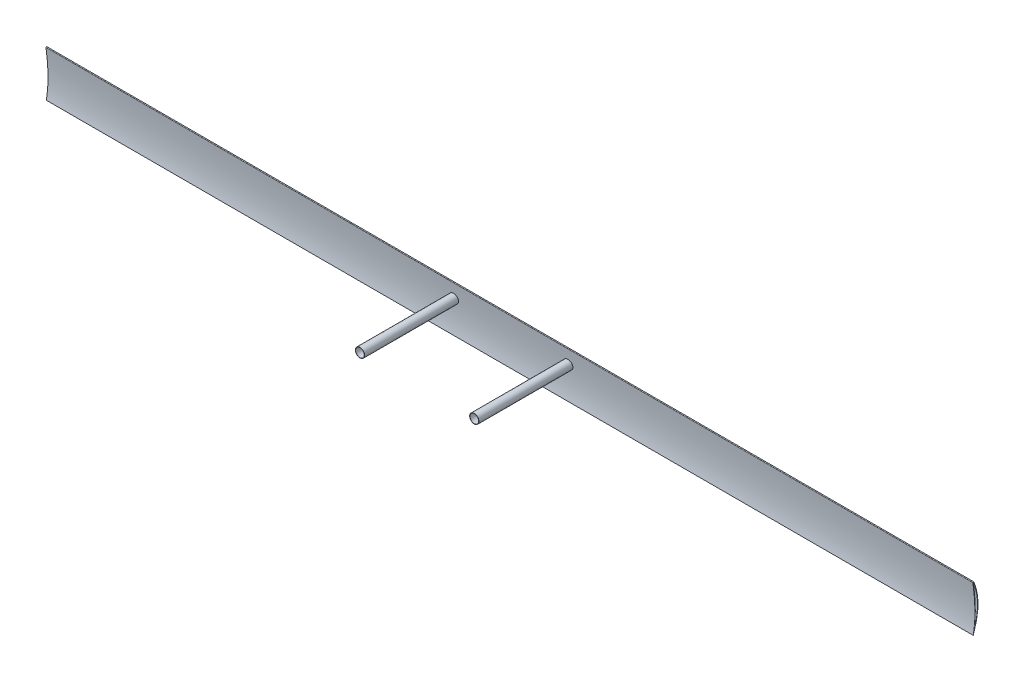
SolidWorks part; units mm, degrees
material "Hexcel AS4C (3000 Filaments)"
ref_plane "前基準面" through (0, 0, 0) normal (0, 0, 1) x (1, 0, 0)
ref_plane "上基準面" through (0, 0, 0) normal (0, 1, 0) x (1, 0, 0)
ref_plane "右基準面" through (0, 0, 0) normal (1, 0, 0) x (0, 0, -1)
sketch "草圖1" plane through (0, 0, 0) normal (0, 1, 0) x (1, 0, 0)
  line L0 (-1500, 0) -> (1500, 0)
  point P3 (0, 0)
  dimension "D1" = 3000
sketch "草圖2" plane through (0, 0, 0) normal (1, 0, 0) x (0, 0, -1)
  line L0 (0, 50) -> (0, -100) construction
  line L1 (13.8985, 3.3596) -> (3.9565, 2.3125) construction
  circle A0 centre (0.3988, 48.554) radius 1.5 construction
  circle A1 centre (8.9403, 2.7146) radius 5 construction
  circle A2 centre (9.6203, -43.8108) radius 4 construction
  arc A3 (-1.0886, 48.3599) -> (1.7944, 49.1037) centre (0.3988, 48.554) cw
  arc A4 (0.847, 48.7757) -> (-0.0918, 48.4573) centre (0.3988, 48.554) ccw
  spline S0 degree 1 poles (0, 50) (0, -100) knots 0 0 1 1 construction
  spline S1 degree 2 poles (0, 50) (20.6039, -23.9685) (0, -100) knots 0 0 0 1 1 1 construction
  spline S2 degree 3 poles (1.7944, 49.1037) (21.8961, -1.9331) (18.1949, -45.1346) (0, -100) knots 0 0 0 0 1 1 1 1
  spline S3 degree 3 poles (-1.0886, 48.3599) (5.3448, -0.9398) (9.7005, -50.0585) (0, -100) knots 0 0 0 0 1 1 1 1
  spline S4 degree 3 poles (0.847, 48.7757) (2.6722, 45.0855) (23.0007, -18.0384) (8.1403, -68.0766) (3.6535, -85.0678) knots 0 0 0 0 0.343942 1 1 1 1
  spline S5 degree 3 poles (-0.0918, 48.4573) (0.9985, 42.9265) (9.152, -17.1272) (5.8098, -70.6891) (3.6535, -85.0678) knots 0 0 0 0 0.343393 1 1 1 1
  dimension "D1" = 3
  dimension "D6" = 1
  dimension "D2" = 150
  dimension "D3" = 50
extrude "填料-伸長1" add sketch "草圖2" along normal up to vertex (1500 mm away) and the other way up to vertex (1500 mm away) up to point (1500, 0, 0) other way up to point (-1500, 0, 0)
ref_plane "平面1" through (0, 0, 200) normal (0, 0, 1) x (1, 0, 0)
sketch "草圖3" plane through (0, 0, 200) normal (0, 0, 1) x (1, 0, 0)
  line L0 (-1500, 0) -> (1500, 0) construction
  line L1 (-185, 0) -> (185, 0) construction
  circle A0 centre (185, 0) radius 15
  circle A1 centre (-185, 0) radius 15
  circle A2 centre (185, 0) radius 14
  circle A3 centre (-185, 0) radius 14
  point P6 (0, 0)
  dimension "D1" = 30
  dimension "D3" = 1
  dimension "D2" = 370
extrude "填料-伸長2" add sketch "草圖3" against normal up to surface and the other way blind 100 up to face at (0, 11.2699, 0.8164)
ref_plane "平面2" through (0, 0, -20) normal (0, 0, 1) x (1, 0, 0)
curve "曲線1"
  spline degree 3 poles (149.1065, 0.1017, 0) (150.2196, -0.0437, 0) (149.135, 0.2489, 0) (148.2582, 0.5567, 0) (146.0923, 1.1965, 0) (143.4195, 1.9978, 0) (139.8974, 3.005, 0) (135.7082, 4.154, 0) (130.8404, 5.4202, 0) (125.3584, 6.7539, 0) (119.317, 8.1207, 0) (112.7765, 9.4732, 0) (105.8082, 10.7736, 0) (98.4853, 11.9821, 0) (90.8867, 13.0635, 0) (83.0963, 13.9879, 0) (75.2009, 14.7297, 0) (67.2867, 15.2583, 0) (59.4021, 15.5949, 0) (51.6307, 15.5985, 0) (44.0772, 15.1999, 0) (36.8788, 14.4542, 0) (30.1283, 13.3973, 0) (23.9108, 12.0837, 0) (18.3003, 10.5813, 0) (13.3638, 8.9553, 0) (9.152, 7.2857, 0) (5.7118, 5.628, 0) (3.0538, 4.0665, 0) (1.2116, 2.6133, 0) (0.0851, 1.3376, 0) (-0.1805, -0.0525, 0) (0.7965, -1.0705, 0) (2.413, -1.5314, 0) (4.6951, -1.8007, 0) (7.6882, -1.8133, 0) (11.3621, -1.6287, 0) (15.68, -1.2602, 0) (20.5924, -0.756, 0) (26.0492, -0.1597, 0) (31.9924, 0.4836, 0) (38.3682, 1.1208, 0) (45.1152, 1.6962, 0) (52.1754, 2.1713, 0) (59.5253, 2.4861, 0) (67.096, 2.6625, 0) (74.8069, 2.8196, 0) (82.5373, 2.8993, 0) (90.2002, 2.9074, 0) (97.7131, 2.8344, 0) (104.994, 2.6857, 0) (111.9628, 2.4672, 0) (118.5419, 2.1942, 0) (124.6567, 1.8797, 0) (130.2345, 1.5456, 0) (135.2162, 1.2065, 0) (139.5235, 0.8875, 0) (143.1607, 0.5942, 0) (145.9334, 0.3654, 0) (148.178, 0.1527, 0) (149.1065, 0.1017, 0) (150.2196, -0.0437, 0) (149.135, 0.2489, 0) knots -0.012269 -0.005489 -0.001366 0 0.001375 0.005484 0.012273 0.021682 0.033581 0.047831 0.064306 0.082777 0.103064 0.124929 0.148149 0.172445 0.197572 0.223269 0.249228 0.275186 0.300901 0.326463 0.351222 0.374906 0.39727 0.418072 0.43708 0.454093 0.46892 0.481392 0.491447 0.499024 0.504294 0.507922 0.51154 0.516781 0.524216 0.533992 0.546034 0.56022 0.576403 0.594371 0.613951 0.634917 0.657089 0.68023 0.704175 0.72909 0.754354 0.779668 0.80476 0.829359 0.853209 0.876041 0.897604 0.917662 0.93597 0.95231 0.966503 0.97835 0.987731 0.994511 0.998634 1 1.001375 1.005484 1.012273 periodic
